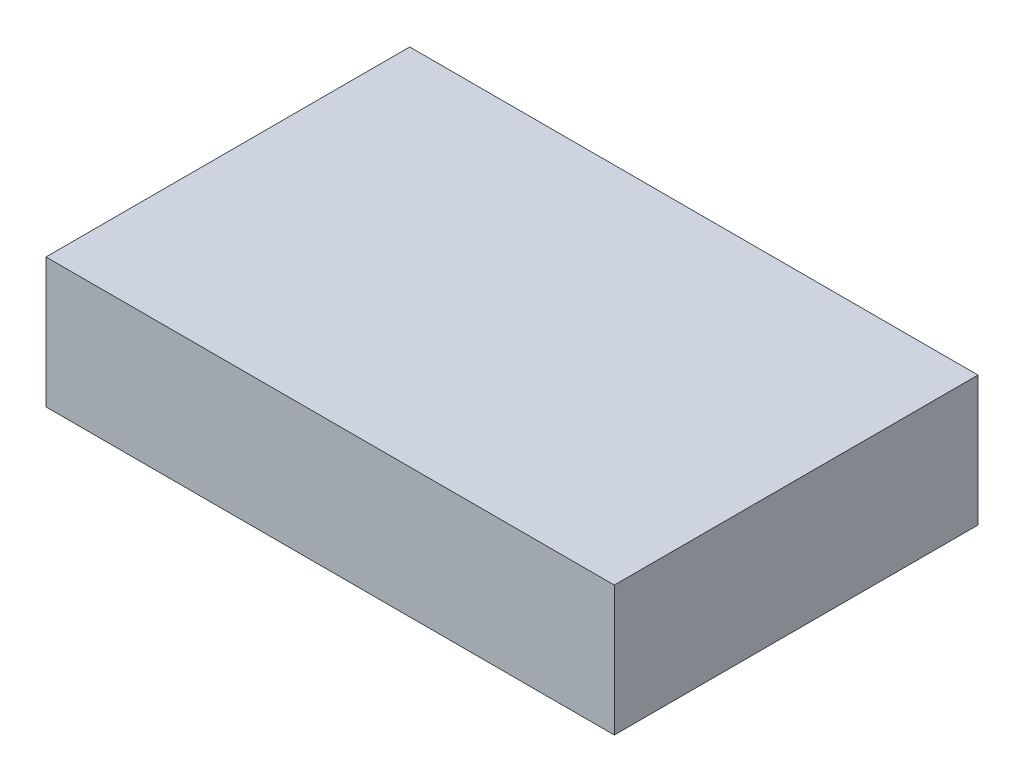
SolidWorks part; units mm, degrees
ref_plane "Front Plane" through (0, 0, 0) normal (0, 0, 1) x (1, 0, 0)
ref_plane "Top Plane" through (0, 0, 0) normal (0, 1, 0) x (1, 0, 0)
ref_plane "Right Plane" through (0, 0, 0) normal (1, 0, 0) x (0, 0, -1)
sketch "Sketch1" plane through (0, 0, 0) normal (0, 1, 0) x (1, 0, 0)
  line L1 (-87.5, -56) -> (87.5, -56)
  line L2 (-87.5, -56) -> (-87.5, 56)
  line L3 (-87.5, 56) -> (87.5, 56)
  line L4 (87.5, -56) -> (87.5, 56)
  line L5 (-87.5, -56) -> (87.5, 56) construction
  line L6 (-87.5, 56) -> (87.5, -56) construction
  point P0 (0, 0)
  dimension "D1" = 112
  dimension "D2" = 175
extrude "Boss-Extrude1" add sketch "Sketch1" along normal mid plane 40
